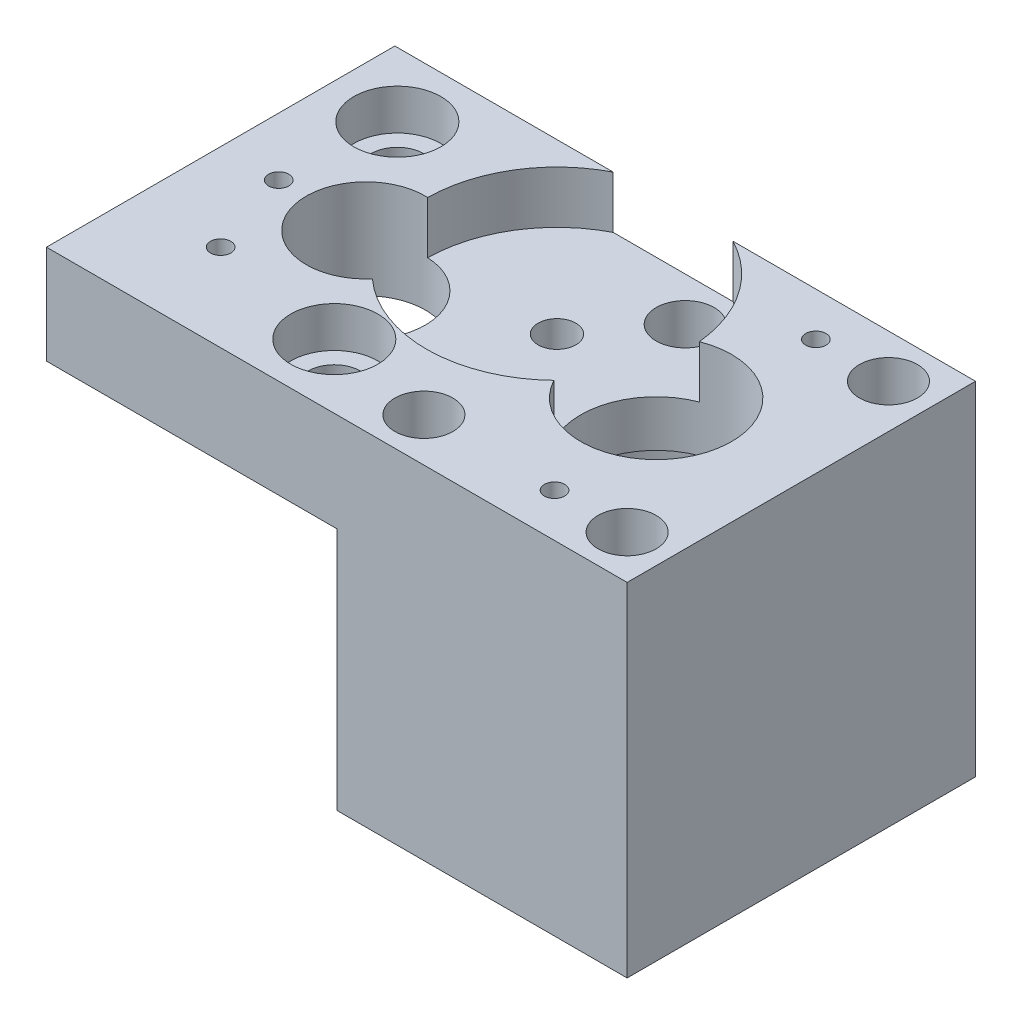
SolidWorks part; units mm, degrees
ref_plane "前视基准面" through (0, 0, 0) normal (0, 0, 1) x (1, 0, 0)
ref_plane "上视基准面" through (0, 0, 0) normal (0, 1, 0) x (1, 0, 0)
ref_plane "右视基准面" through (0, 0, 0) normal (1, 0, 0) x (0, 0, -1)
other "Configuration Table"
sketch "草图1" plane through (0, 0, 0) normal (0, 1, 0) x (1, 0, 0)
  line L1 (0, 0) -> (20, 0)
  line L2 (0, 0) -> (0, -12)
  line L3 (0, -12) -> (20, -12)
  line L4 (20, 0) -> (20, -12)
  circle A0 centre (5, -6) radius 2.05
  circle A4 centre (15, -6) radius 2.6
  circle A5 centre (9.5826, -4) radius 0.65
  point P7 (0, 0)
  point P9 (0, 0)
  point P12 (0, 0)
  point P14 (0, 0)
  point P16 (0, 0)
  dimension "D2" = 4.1
  dimension "D3" = 1.3
  dimension "D4" = 20
  dimension "D5" = 5.2
  dimension "D9" = 5
  dimension "D10" = 6
  dimension "D11" = 12
extrude "凸台-拉伸1" add sketch "草图1" along normal blind 1.6 contours L1 L4 L3 L2 | A0 | A4 | A5
sketch "草图3" plane through (0, 1.6, 0) normal (0, 1, 0) x (1, 0, 0)
  line L1 (0, 0) -> (20, 0)
  line L2 (0, 0) -> (0, -12)
  line L3 (0, -12) -> (20, -12)
  line L4 (20, 0) -> (20, -12)
  circle A0 centre (5, -6) radius 2.05
  circle A1 centre (5, -6) radius 2.05 construction
  circle A4 centre (9.5826, -4) radius 4.5
  circle A10 centre (9.5826, -4) radius 0.65 construction
  circle M4 centre (15, -6) radius 2.6
  line M5 (0, 0) -> (0, -12)
  line M6 (0, -12) -> (20, -12)
  line M7 (20, -12) -> (20, 0)
  line M8 (20, 0) -> (0, 0)
  dimension "D1" = 9
sketch "草图5" plane through (0, 0, 0) normal (0, 1, 0) x (1, 0, 0)
  circle A0 centre (2.3, -2.2142) radius 0.9
  circle A1 centre (7.7, -9.7858) radius 0.9
  circle A4 centre (2.3, -2.2142) radius 1.5
  circle A5 centre (7.7, -9.7858) radius 1.5
  dimension "D1" = 1.8
  dimension "D2" = 3
extrude "凸台-拉伸3" add sketch "草图3" along normal blind 1.8 contours A4 A0 M4 M8 M5 M6 M7 region at (3.7605, 1.6, 0.2332)
extrude "切除-拉伸1" cut sketch "草图5" against normal through all from surface contours A1 | A0 starting at face at (9.886, 3.4, 4.9336)
extrude "切除-拉伸3" cut sketch "草图5<10>" against normal offset from surface (1.4 mm away) 2 from surface contours A5 | A4 up to face at (7.7, 0, 10.6858) starting at face at (7.7, 3.4, 10.6858)
sketch "草图5<10>" plane through (0, 0, 0) normal (0, 1, 0) x (1, 0, 0) same geometry as "草图5"
sketch "草图7" plane through (0, 3.4, 0) normal (0, 1, 0) x (1, 0, 0)
  line L0 (0, -12) -> (20, -12) construction
  line L1 (0, 0) -> (0, -12) construction
  line L2 (20, 0) -> (11.6441, 0) construction
  line L3 (20, -12) -> (20, 0) construction
  line L4 (7.521, 0) -> (0, 0) construction
  circle A0 centre (2, -6) radius 0.35
  circle A1 centre (3, -9) radius 0.35
  circle A2 centre (16, -1.5) radius 0.35
  circle A3 centre (16, -10.5) radius 0.35
  point P8 (0, 0)
  point P9 (18.4858, -10.654)
  point P10 (0, 0)
  point P11 (18.1181, -1.8644)
  point P12 (0, 0)
  point P17 (0, -11.8146)
  point P20 (0, 0)
  point P23 (0, 0)
  dimension "D1" = 0.7
  dimension "D2" = 3
  dimension "D3" = 3
  dimension "D4" = 1.5
  dimension "D5" = 1.5
  dimension "D6" = 4
  dimension "D7" = 4
  dimension "D8" = 2
  dimension "D9" = 6
extrude "切除-拉伸4" cut sketch "草图7" against normal blind 2
sketch "草图8" plane through (0, 0, 0) normal (0, -1, 0) x (1, 0, 0)
  line L0 (2.5108, 6) -> (22.5108, 6) construction
  line L3 (20, 0) -> (20, 12) construction
  line L4 (0, 0) -> (20, 0) construction
  line L5 (20, 12) -> (10, 12)
  line L6 (20, 12) -> (20, 0)
  line L7 (20, 0) -> (10, 0)
  line L8 (10, 12) -> (10, 0)
  circle A0 centre (15, 6) radius 3.5
  dimension "D2" = 7
  dimension "D1" = 5
  dimension "D3" = 10
extrude "凸台-拉伸4" add sketch "草图8" along normal blind 8.4 contours L7 L8 L5 L6 | A0
sketch "草图9" plane through (0, -8.4, 0) normal (0, -1, 0) x (1, 0, 0)
  line L0 (20, 12) -> (10, 12) construction
  line L1 (10, 12) -> (10, 0) construction
  line L2 (20, 0) -> (10, 0) construction
  line L3 (20, 12) -> (20, 0) construction
  circle A0 centre (11.5, 10.5) radius 1
  circle A1 centre (11.5, 10.5) radius 0.7
  circle A2 centre (18.5, 10.5) radius 1
  circle A3 centre (18.5, 10.5) radius 0.7
  circle A4 centre (11.5, 1.5) radius 1
  circle A5 centre (11.5, 1.5) radius 0.7
  circle A6 centre (18.5, 1.5) radius 0.7
  circle A7 centre (18.5, 1.5) radius 1
  point P12 (13.5222, 10.3318)
  point P13 (17.0004, 10.5278)
  point P14 (13.1303, 1.1708)
  point P15 (17.1719, 0.7544)
  point P24 (0, 0)
  point P25 (0, 0)
  point P26 (0, 0)
  dimension "D5" = 1.4
  dimension "D6" = 2
  dimension "D1" = 1.5
  dimension "D2" = 1.5
  dimension "D3" = 1.5
  dimension "D4" = 1.5
extrude "切除-拉伸5" cut sketch "草图9" against normal through all contours A3 | A1 | A5 | A6
extrude "切除-拉伸6" cut sketch "草图9<3>" along normal offset from surface (8.8 mm away) 3 from surface up to face at (18.5, -8.4, 0.8) starting at face at (18.5, 3.4, 0.8)
sketch "草图9<3>" plane through (0, -8.4, 0) normal (0, -1, 0) x (1, 0, 0) same geometry as "草图9"
